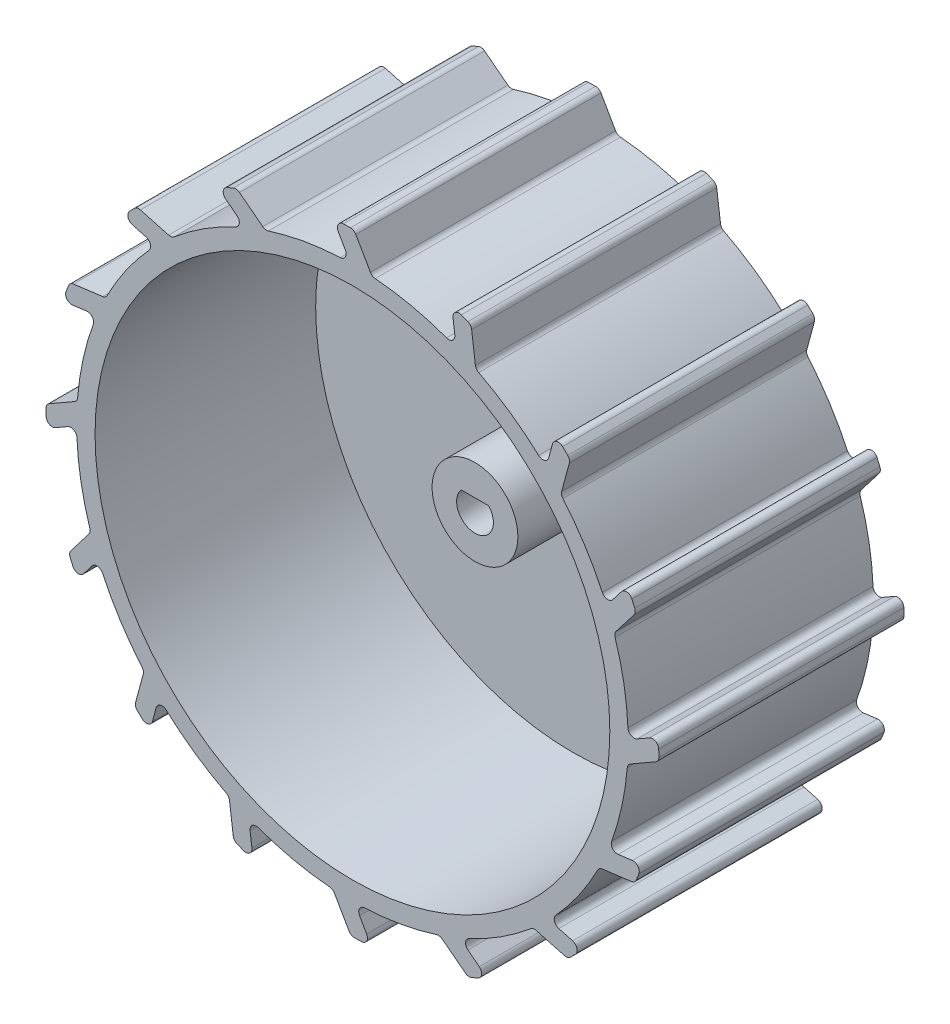
SolidWorks part; units mm, degrees
ref_plane "Front Plane" through (0, 0, 0) normal (0, 0, 1) x (1, 0, 0)
ref_plane "Top Plane" through (0, 0, 0) normal (0, 1, 0) x (1, 0, 0)
ref_plane "Right Plane" through (0, 0, 0) normal (1, 0, 0) x (0, 0, -1)
ref_axis "X" through (-88.99, 0, 0) along (1, 0, 0)
ref_axis "Y" through (0, 55, 0) along (0, -1, 0)
ref_axis "Z" through (0, 0, -88.99) along (0, 0, 1)
sketch "Sketch1" plane through (0, 0, 0) normal (0, 0, 1) x (1, 0, 0)
  line L0 (-1.5701, 24.9506) -> (-0.1619, 22.4994)
  line L1 (0.1316, 24.9997) -> (1.6004, 22.443)
  line L2 (-0.866, 23.725) -> (0.866, 23.7213) construction
  line L3 (0, 23.7232) -> (0, 0) construction
  line L4 (-1.118, 1) -> (1.118, 1)
  circle A0 centre (0, 0) radius 25
  circle A1 centre (0, 0) radius 1.5
  circle A2 centre (0, 0) radius 22.5
  circle A3 centre (0, 0) radius 21
  circle A4 centre (0, 0) radius 3.5
  dimension "D1" = 50
  dimension "D2" = 3
  dimension "D4" = 1.5
  dimension "D5" = 60
  dimension "D8" = 1
  dimension "D3" = 2.5
  dimension "D6" = 1.5
  dimension "D7" = 2
extrude "Boss-Extrude2" add sketch "Sketch1" along normal blind 2 contours A3 A4 region at (-20.406, 0, 0)
extrude "Boss-Extrude3" add sketch "Sketch1<4>" along normal blind 20 contours A2 A3 region at (0.6995, 21.8524, 0)
sketch "Sketch1<4>" plane through (0, 0, 0) normal (0, 0, 1) x (1, 0, 0) same geometry as "Sketch1"
extrude "Boss-Extrude4" add sketch "Sketch1<5>" along normal up to surface (20 mm away) contours A2 L1 A0 L0 region at (0, 23.7338, 0) up to face at (21, 0, 20)
sketch "Sketch1<5>" plane through (0, 0, 0) normal (0, 0, 1) x (1, 0, 0) same geometry as "Sketch1"
fillet "Fillet1" radius 0.5 4 edges at (-0.1619, 22.4994, 10) (1.6004, 22.443, 10) (0.1316, 24.9997, 10) (-1.5701, 24.9506, 10)
pattern_circular "CirPattern1" count 16 over 360 about axis through (0, 0, -88.99) along (0, 0, 1) of "Boss-Extrude4", "Fillet1"
extrude "Boss-Extrude5" add sketch "Sketch1<6>" along normal blind 10 contours A4 A1 | L4 A1 region at (0, 1.2032, 0) region at (-3.401, 0, 0)
sketch "Sketch1<6>" plane through (0, 0, 0) normal (0, 0, 1) x (1, 0, 0) same geometry as "Sketch1"
draft "Draft1" type of draft neutral plane draft angle 1 faces to draft 2 face at (0, 1, 5) face at (0, -0.25, 5) neutral plane through (0, 0, 10) neutral plane normal (0, 0, 1) reverse direction yes parameters "D1"=1
